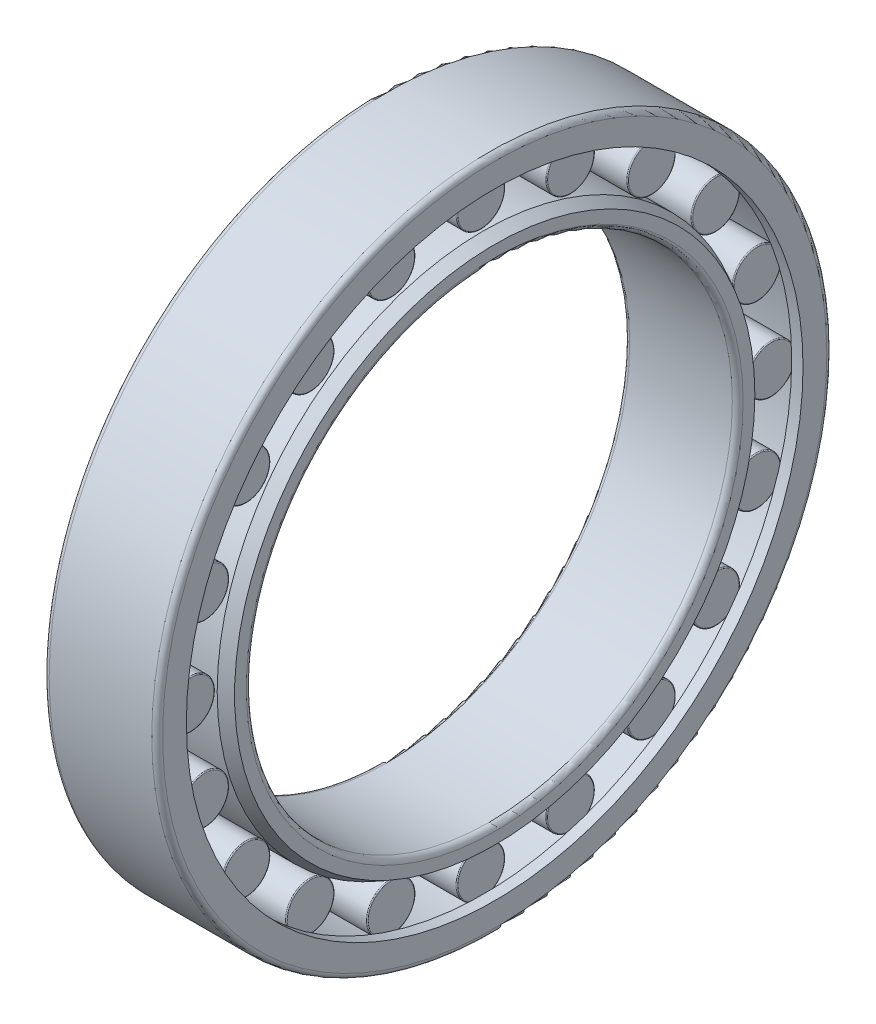
SolidWorks part; units mm, degrees
ref_plane "Plane1" through (0, 0, 0) normal (0, 0, 1) x (1, 0, 0)
ref_plane "Plane2" through (0, 0, 0) normal (0, 1, 0) x (1, 0, 0)
ref_plane "Plane3" through (0, 0, 0) normal (1, 0, 0) x (0, 0, -1)
sketch "Clipboard" plane through (0, 0, 0) normal (0, 0, 1) x (1, 0, 0)
  line L0 (-10, 0) -> (10, 0) construction
  line L1 (0, 0) -> (185.2698, -67.4327)
  line L2 (0, 0) -> (101.017, 36.7672)
  line L3 (0, 0) -> (218.798, -79.636)
  line L4 (0, 0) -> (-22.3471, -0.7804)
  dimension "Race_OD" = 232.84
  dimension "Race_ID" = 197.16
sketch "OutRacSke" plane through (0, 0, 0) normal (0, 0, 1) x (1, 0, 0)
  line L0 (-16.8, 114.1887) -> (-21, 114.1887)
  line L1 (-21, 114.1887) -> (-21, 123)
  line L2 (-19, 125) -> (19, 125)
  line L3 (21, 123) -> (21, 114.1888)
  line L4 (21, 114.1888) -> (16.8, 114.1888)
  line L5 (16.8, 114.1888) -> (16.8, 116.42)
  line L6 (16.8, 116.42) -> (-16.8, 116.42)
  line L7 (-16.8, 116.42) -> (-16.8, 114.1887)
  line L8 (-90, 0) -> (90, 0) construction
  arc A0 (-21, 123) -> (-19, 125) centre (-19, 123) cw
  arc A1 (19, 125) -> (21, 123) centre (19, 123) cw
  dimension "Race_OD" = 232.84
  dimension "radius" = 2
  dimension "halfWidth" = 21
  dimension "groove_dp" = 2.2313
  dimension "Cyl_Len" = 33.6
revolve "OuterRace" add sketch "OutRacSke" angle 360 about L8 reverse direction yes
sketch "RolDetSke" plane through (0, 0, 0) normal (0, 0, 1) x (1, 0, 0)
  line L0 (-15.96, 116.068) -> (-15.96, 107.5)
  line L1 (-15.96, 107.5) -> (15.96, 107.5)
  line L2 (15.96, 107.5) -> (15.96, 116.068)
  line L3 (15.603, 116.425) -> (-15.603, 116.425)
  line L4 (-33.6, 107.5) -> (33.6, 107.5) construction
  arc A0 (15.96, 116.068) -> (15.603, 116.425) centre (15.603, 116.068) ccw
  arc A1 (-15.603, 116.425) -> (-15.96, 116.068) centre (-15.603, 116.068) ccw
  dimension "radius" = 0.357
  dimension "Roller_diameter" = 17.85
  dimension "halfLength" = 15.96
revolve "RollerDetailed" add sketch "RolDetSke" angle 360 about L4 reverse direction yes
ref_axis "Axis1" through (-50, 0, 0) along (1, 0, 0)
sketch "RolSimSke" plane through (0, 101.6, 0) normal (0, 0, 1) x (1, 0, 0)
  line L0 (-15.96, 14.468) -> (-15.96, -2.668)
  line L1 (25.4, -101.6) -> (-25.4, -101.6) construction
  line L2 (15.96, -2.668) -> (15.96, 14.468)
  line L3 (15.603, 14.825) -> (-15.603, 14.825)
  line L5 (15.603, -3.025) -> (-15.603, -3.025)
  arc A0 (15.96, 14.468) -> (15.603, 14.825) centre (15.603, 14.468) ccw
  arc A1 (-15.603, 14.825) -> (-15.96, 14.468) centre (-15.603, 14.468) ccw
  arc A2 (15.96, -2.668) -> (15.603, -3.025) centre (15.603, -2.668) cw
  arc A3 (-15.603, -3.025) -> (-15.96, -2.668) centre (-15.603, -2.668) cw
  dimension "radius" = 0.357
  dimension "D1" = 98.575
  dimension "Roller_diameter" = 17.85
  dimension "halfLength" = 15.96
revolve "RollersSimplified" [suppressed] add sketch "RolSimSke" angle 360 about L1
sketch "InsRacSke" plane through (0, 0, 0) normal (0, 0, 1) x (1, 0, 0)
  line L0 (-16.8, 98.58) -> (-21, 96.3487)
  line L1 (-21, 96.3487) -> (-21, 92)
  line L2 (-19, 90) -> (19, 90)
  line L3 (21, 92) -> (21, 96.3487)
  line L4 (21, 96.3487) -> (16.8, 98.58)
  line L5 (16.8, 98.58) -> (-16.8, 98.58)
  line L6 (-90, 0) -> (90, 0) construction
  arc A0 (-21, 92) -> (-19, 90) centre (-19, 92) ccw
  arc A1 (19, 90) -> (21, 92) centre (19, 92) ccw
  dimension "radius" = 2
  dimension "Race_ID" = 197.16
  dimension "Width" = 42
  dimension "halfWidth" = 21
  dimension "groove_dp" = 2.2313
  dimension "Cyl_Len" = 33.6
revolve "InnerRace" add sketch "InsRacSke" angle 360 about L6 reverse direction yes
pattern_circular "RollersDetailed" count 20 every 18 about axis through (-50, 0, 0) along (1, 0, 0) of "RollerDetailed"
sketch "CagSpiSke" plane through (0, 0, 0) normal (0, 0, 1) x (1, 0, 0)
  line L0 (18.9, 105.2687) -> (18.9, 109.7313)
  line L1 (18.9, 109.7313) -> (-18.9, 109.7313)
  line L2 (-18.9, 109.7313) -> (-18.9, 105.2687)
  line L3 (-18.9, 105.2687) -> (18.9, 105.2687)
  line L4 (-90, 0) -> (90, 0) construction
revolve "CageSpine" [suppressed] add sketch "CagSpiSke" angle 360 about L4
equation "\"CLdia@Clipboard\" =  ( \"Race_OD@Clipboard\" + \"Race_ID@Clipboard\" )  / 4"
equation "\"Race_OD@OutRacSke\" = \"Race_OD@Clipboard\""
equation "\"halfCylLen@OutRacSke\" = \"Cyl_Len@OutRacSke\" / 2"
equation "\"RolCLRad@RolDetSke\" = \"CLdia@Clipboard\""
equation "\"Roller_diameter@RolDetSke\" =  ( \"Race_OD@Clipboard\" - \"Race_ID@Clipboard\" )  / 2 + .01"
equation "\"Roller_diameter@RolSimSke\" =  ( \"Race_OD@Clipboard\" - \"Race_ID@Clipboard\" )  / 2 + .01"
equation "\"radius@RolDetSke\" = \"Roller_diameter@RolDetSke\" / 50"
equation "\"Length@RolDetSke\" = \"Cyl_Len@OutRacSke\" * .95"
equation "\"halfLength@RolDetSke\" = \"Length@RolDetSke\" / 2"
equation "\"thickness@CagSpiSke\"  = \"Roller_diameter@RolDetSke\" * .25"
equation "\"Cag_IR@CagSpiSke\" =  \"RolCLRad@RolDetSke\" * 2 - \"thickness@CagSpiSke\""
equation "\"Rol_Length@RolSimSke\" = \"Cyl_Len@InsRacSke\" * .95"
equation "\"halfLength@RolSimSke\" = \"Rol_Length@RolSimSke\" / 2"
equation "\"radius@RolSimSke\" = \"radius@RolDetSke\""
equation "\"D1@RolSimSke\" = \"CLdia@Clipboard\" -  ( \"Roller_diameter@RolSimSke\" / 2 ) "
equation "\"Max_count@Clipboard\" = int( 3.14159265 / atn(( \"Roller_diameter@RolDetSke\" / 2) / sqr( \"RolCLRad@RolDetSke\"  *  \"RolCLRad@RolDetSke\" - ( \"Roller_diameter@RolDetSke\" / 2) *  ( \"Roller_diameter@RolDetSke\" / 2))))"
equation "\"Max_count@Clipboard\" = ((sgn( \"Max_count@Clipboard\" - \"Count@Clipboard\" )-1)*( \"Max_count@Clipboard\" - \"Count@Clipboard\" ))/-2+ \"Count@Clipboard\""
equation "\"Count@RollersDetailed\" = int( \"Show_count@Clipboard\" ) "
equation "\"Count@RollersDetailed\" = ((sgn( \"Count@RollersDetailed\" - \"Max_count@Clipboard\" )-1)*( \"Count@RollersDetailed\" - \"Max_count@Clipboard\" ))/-2+ \"Max_count@Clipboard\""
equation "\"Count@RollersDetailed\" = ((sgn( \"Count@RollersDetailed\" - \"Min_count@Clipboard\" )+1)*( \"Count@RollersDetailed\" - \"Min_count@Clipboard\"))/2 +\"Min_count@Clipboard\""
equation "\"Angle@RollersDetailed\" = 360.0 / \"Max_count@Clipboard\""
equation "\"radius@InsRacSke\" = \"radius@OutRacSke\""
equation "\"groove_dp@InsRacSke\" = \"groove_dp@OutRacSke\""
equation "\"Width@InsRacSke\" = \"Width@OutRacSke\""
equation "\"halfWidth@OutRacSke\" = \"Width@OutRacSke\" / 2"
equation "\"halfWidth@InsRacSke\" = \"Width@InsRacSke\" / 2"
equation "\"Race_ID@InsRacSke\" = \"Race_ID@Clipboard\""
equation "\"Cyl_Len@InsRacSke\" = \"Cyl_Len@OutRacSke\""
equation "\"Angle@CageSpine\" =  \"Angle@RollersDetailed\" * ( \"Count@RollersDetailed\" -1 + int( \"Count@RollersDetailed\" / \"Max_count@Clipboard\" ) )  + 0.001 -  int( \"Count@RollersDetailed\" / \"Max_count@Clipboard\" ) * 0.001"
equation "\"Angle@CageSpine\" =  \"Angle@CageSpine\" * int( \"Min_count@Clipboard\" / 2) + int(1 / \"Min_count@Clipboard\")  * 0.001"
equation "\"width@CagSpiSke\" =   ( \"Width@InsRacSke\" + \"Cyl_Len@InsRacSke\" )  / 2"
equation "\"halfwidth@CagSpiSke\" = \"width@CagSpiSke\" / 2"
